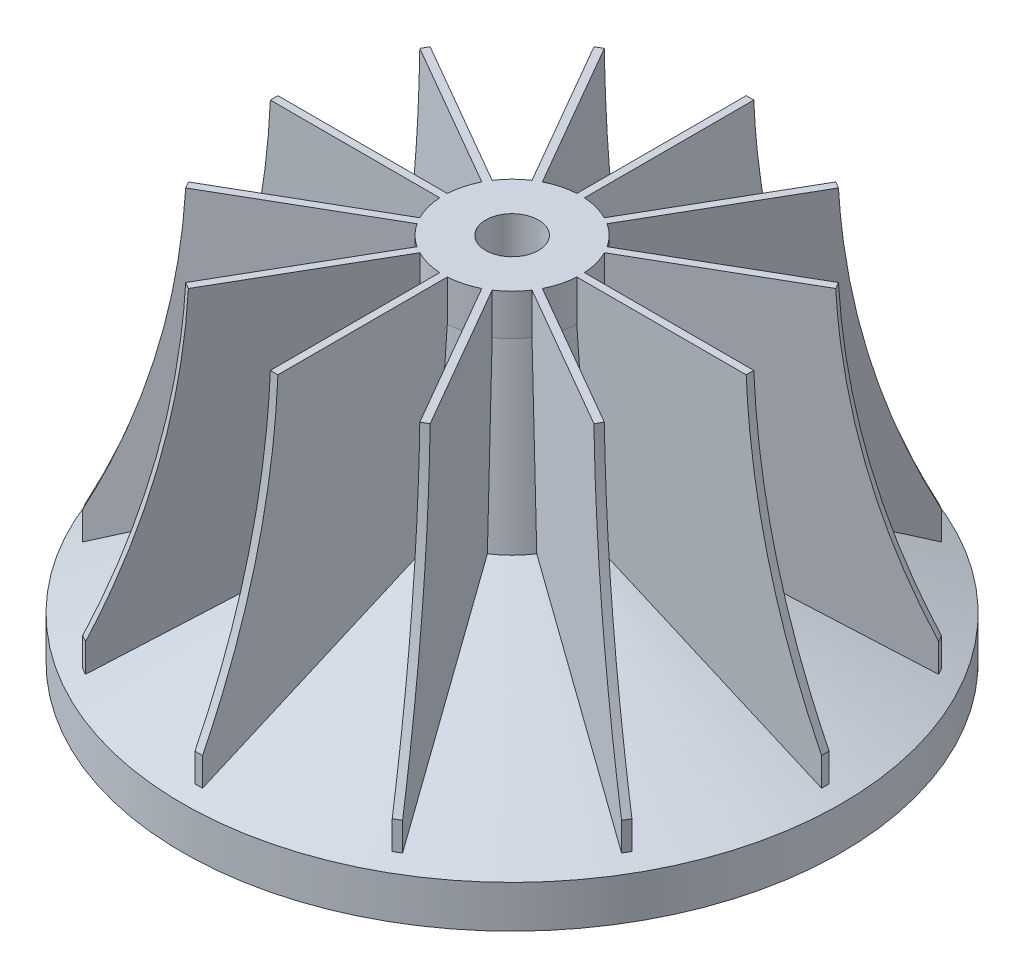
SolidWorks part; units mm, degrees
ref_plane "Front Plane" through (0, 0, 0) normal (0, 0, 1) x (1, 0, 0)
ref_plane "Top Plane" through (0, 0, 0) normal (0, 1, 0) x (1, 0, 0)
ref_plane "Right Plane" through (0, 0, 0) normal (1, 0, 0) x (0, 0, -1)
sketch "Sketch1" plane through (0, 0, 0) normal (0, 0, 1) x (1, 0, 0)
  line L7 (0, 0) -> (0, 37.1175) construction
  line L8 (0, 0) -> (-39.624, 0)
  line L9 (-39.624, 0) -> (-39.624, 5.08)
  line L11 (-39.624, 5.08) -> (-9.8229, 18.0693)
  line L12 (-9.8229, 18.0693) -> (-8.255, 39.5182)
  line L13 (-8.255, 39.5182) -> (-8.255, 44.45)
  line L14 (-8.255, 44.45) -> (0, 44.45)
  line L15 (0, 44.45) -> (0, 0)
  point P1 (-10.7068, 21.4281)
  point P10 (0, 0)
  point P11 (0, 0)
  point P12 (-34.3856, 5.08)
  point P13 (0, 0)
  point P14 (0, 0)
  point P15 (-34.4399, 5.08)
  point P16 (0, 0)
  point P17 (0, 0)
  point P18 (-34.4399, 5.08)
  point P19 (0, 0)
  point P20 (-34.4399, 5.08)
  point P21 (-34.4399, 5.08)
  point P22 (-39.624, 5.4462)
  point P23 (-9.8229, 18.0693)
  dimension "D1" = 39.624
  dimension "D2" = 8.255
  dimension "D3" = 44.45
  dimension "D4" = 5.08
revolve "Revolve1" add sketch "Sketch1" angle 360 about L7
ref_plane "Plane1" through (0, 44.45, 0) normal (0, 1, 0) x (1, 0, 0)
sketch "Sketch3" plane through (0, 44.45, 0) normal (0, 1, 0) x (1, 0, 0)
  line L6 (0.4559, -37.6702) -> (0.456, -8.2062)
  line L7 (-0.4559, -37.6702) -> (-0.4559, -8.2062)
  line L9 (-0.4559, -37.6702) -> (0.4559, -37.6702)
  line L12 (0, -55) -> (0, 55) construction
  circle A2 centre (0, 0) radius 8.255 construction
  spline S0 degree 2 poles (-0.4559, -8.2062) (0, -8.3038) (0.456, -8.2062) knots 0 0 0 1 1 1
  dimension "D1" = 29.464
extrude "Boss-Extrude5" add sketch "Sketch3" against normal up to next
pattern_circular "CirPattern8" count 12 over 360 about axis through (0, 18.0693, 0) along (0, 1, 0) of "Boss-Extrude5"
sketch "Sketch7" plane through (0, 0, 0) normal (1, 0, 0) x (0, 0, -1)
  line L1 (-37.6702, 5.9304) -> (-37.6702, 44.45) construction
  line L2 (-42.1334, 53.4862) -> (-28.575, 53.4862)
  line L4 (0, 0) -> (0, 61.1174) construction
  line L6 (-42.1334, 53.4862) -> (-42.6847, 9.3395)
  line L7 (-42.6847, 9.3395) -> (-37.6702, 9.3395)
  line L8 (-28.575, 53.4862) -> (-28.575, 45.2583)
  spline S0 degree 2 poles (-28.575, 45.2583) (-29.26, 26.3077) (-37.6702, 9.3395) knots 0 0 0 1 1 1
  point P11 (-28.575, 45.2583)
  dimension "D1" = 28.575
revolve "Cut-Revolve3" cut sketch "Sketch7" angle 360 about L4
sketch "Sketch4" plane through (0, 0, 0) normal (1, 0, 0) x (0, 0, -1)
  line L5 (0, 0) -> (0, 72.6591) construction
  line L6 (-18.4402, 47.752) -> (-8.255, 47.752)
  line L8 (-8.255, 47.752) -> (-8.255, 53.2514)
  line L10 (-18.4402, 5.9304) -> (-18.4402, 9.3395) construction
  line L13 (-37.6702, 5.9304) -> (-37.6702, 9.3395) construction
  line L14 (-37.6702, 7.8709) -> (-37.6702, 53.2514)
  line L17 (-37.6702, 53.2514) -> (-8.255, 53.2514)
  arc A0 (-37.6702, 7.8709) -> (-18.4402, 47.752) centre (-68.3352, 47.2337) ccw
  dimension "D2" = 8.255
sketch "Sketch6" plane through (0, 44.45, 0) normal (0, 1, 0) x (1, 0, 0)
  circle A0 centre (0, 0) radius 3.175
  dimension "D1" = 6.35
extrude "Cut-Extrude1" cut sketch "Sketch6" against normal up to next
equation "\"1.90n\"=2"
